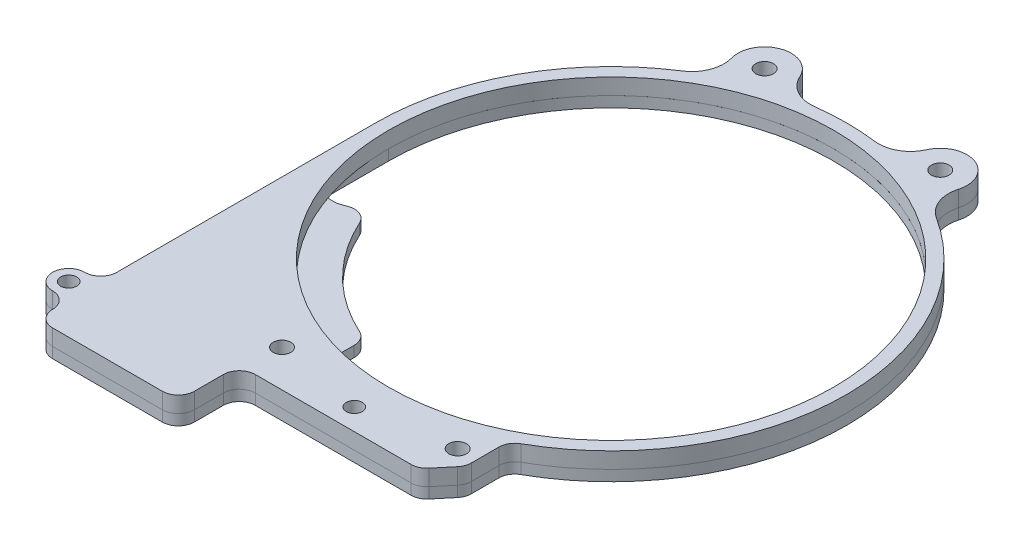
SolidWorks part; units mm, degrees
material "Thornel Mat VMA"
ref_plane "前视基准面" through (0, 0, 0) normal (0, 0, 1) x (1, 0, 0)
ref_plane "上视基准面" through (0, 0, 0) normal (0, 1, 0) x (1, 0, 0)
ref_plane "右视基准面" through (0, 0, 0) normal (1, 0, 0) x (0, 0, -1)
other "Configuration Table"
sketch "草图1" plane through (0, 0, 0) normal (0, 1, 0) x (1, 0, 0)
  line L0 (-33.3591, -12.1417) -> (-37.5877, -13.6808)
  line L1 (-13, -33.0341) -> (-13, -39.5166)
  line L2 (0, 0) -> (0, -48) construction
  line L3 (-37.5877, -13.6808) -> (-41.6, -13.6808)
  line L4 (0, 0) -> (-48, 0) construction
  line L5 (-44, 3.1363) -> (-44, -21.8637)
  line L6 (-44, -52) -> (16, -52)
  line L7 (-44, -27.8637) -> (-44, -52)
  line L8 (-44, 3.1363) -> (-44, 0)
  line L9 (0, 0) -> (16.417, 45.1052) construction
  line L10 (-44, -21.8637) -> (-44, -27.8637)
  line L11 (-41.6, 0) -> (-41.6, -13.6808)
  arc A0 (44, 0) -> (23.7553, 37.0363) centre (0, 0) ccw
  arc A1 (-13, -39.5166) -> (-41.6, 0) centre (0, 0) ccw
  arc A2 (-33.3591, -12.1417) -> (-13, -33.0341) centre (0, 0) ccw
  arc A3 (44, 0) -> (16, -52) centre (-18.2857, 0) cw
  circle A8 centre (0, -48) radius 1.5
  arc A9 (21.225, 43.7332) -> (11.8518, 47.1447) centre (16.417, 45.1052) ccw
  circle A10 centre (16.417, 45.1052) radius 1.65
  arc A11 (-21.225, 43.7332) -> (-11.8518, 47.1447) centre (-16.417, 45.1052) cw
  arc A13 (-23.7553, 37.0363) -> (-44, 0) centre (0, 0) ccw
  arc A14 (5.6088, 43.641) -> (-5.6088, 43.641) centre (0, 0) ccw
  arc A15 (23.7553, 37.0363) -> (21.225, 43.7332) centre (26.9947, 42.0867) cw
  arc A16 (5.6088, 43.641) -> (11.8518, 47.1447) centre (6.3737, 49.5921) ccw
  arc A17 (-5.6088, 43.641) -> (-11.8518, 47.1447) centre (-6.3737, 49.5921) cw
  arc A18 (-23.7553, 37.0363) -> (-21.225, 43.7332) centre (-26.9947, 42.0867) ccw
  circle A19 centre (-16.417, 45.1052) radius 1.65
  circle A20 centre (16.417, -45.1052) radius 1.65
  circle A21 centre (-16.417, -45.1052) radius 1.65
  point P6 (-13, -36.2753)
  dimension "D1" = 88
  dimension "D2" = 83.2
  dimension "D3" = 35.5
  dimension "D9" = 10
  dimension "D10" = 3.3
  dimension "D13" = 3
  dimension "D16" = 6
  dimension "D4" = 13
  dimension "D5" = 20
  dimension "D6" = 40
  dimension "D7" = 52
  dimension "D8" = 60
  dimension "D11" = 48
  dimension "D12" = 48
  dimension "D14" = 48
  dimension "D15" = 20
extrude "凸台-拉伸1" add sketch "草图1" along normal blind 2 contours A18 A13 L5 L10 L7 L6 A3 A0 A15 A9 A16 A14 A17 A11 A2 L0 L3 A1 L1 A8 A10 A19 region at (-37.4257, 0, -20.4576)
fillet "圆角1" radius 3 5 edges at (-13, 1, 39.5166) (-37.5877, 1, 13.6808) (-33.3591, 1, 12.1417) (-13, 1, 33.0341) (-41.6, 1, 13.6808)
sketch "草图3" plane through (0, 2, 0) normal (0, 1, 0) x (1, 0, 0)
  line L0 (16, -52) -> (20, -47.1918)
  line L1 (20, -47.1918) -> (20, -39.1918)
  line L2 (-44, 0) -> (-44, -52) construction
  circle A0 centre (0, 0) radius 44
  arc M7 (16, -52) -> (44, 0) centre (-18.2857, 0) ccw
  dimension "D1" = 88
  dimension "D2" = 64
  dimension "D3" = 8
extrude "切除-拉伸1" cut sketch "草图3" against normal blind 10 contours A0 L1 L0 M7 region at (29.1032, 2, 35.3583)
sketch "草图5" plane through (0, 2, 0) normal (0, 1, 0) x (1, 0, 0)
  line L0 (-44, 0) -> (-44, -52) construction
  line L1 (-17.5, -52) -> (-44, -52)
  line L2 (-17.5, -52) -> (-17.5, -63.4)
  line L3 (-17.5, -63.4) -> (-44, -63.4)
  line L4 (-44, -52) -> (-44, -63.4)
  line L5 (-44, -52) -> (16, -52) construction
  dimension "D1" = 11.4
  dimension "D2" = 26.5
extrude "凸台-拉伸2" add sketch "草图5" against normal blind 2
sketch "草图6" plane through (0, 2, 0) normal (0, 1, 0) x (1, 0, 0)
  line L1 (-44, -63.4) -> (-17.5, -63.4) construction
  line L2 (-44, 0) -> (-44, -63.4) construction
  line L4 (-50, -57.4) -> (-44, -57.4)
  line L5 (-50, -57.4) -> (-50, -51.4)
  line L6 (-50, -51.4) -> (-44, -51.4)
  line L7 (-44, -57.4) -> (-44, -51.4)
  line L8 (-50, -57.4) -> (-44, -51.4) construction
  line L9 (-50, -51.4) -> (-44, -57.4) construction
  circle A0 centre (-47, -54.4) radius 1.5
  dimension "D1" = 9
  dimension "D2" = 3
  dimension "D3" = 3
extrude "凸台-拉伸3" add sketch "草图6" against normal blind 2
fillet "圆角2" radius 3 10 edges at (-44, 1, 51.4) (-50, 1, 57.4) (-44, 1, 57.4) (-44, 1, 63.4) (-17.5, 1, 63.4) (-17.5, 1, 52) (16, 1, 52) (20, 1, 47.1918) (20, 1, 39.1918) (-50, 1, 51.4)
sketch "草图7" plane through (0, 2, 0) normal (0, 1, 0) x (1, 0, 0)
  line L6 (-41, -63.4) -> (-20.5, -63.4)
  line L7 (-17.5, -60.4) -> (-17.5, -55)
  line L8 (-14.5, -52) -> (14.5933, -52)
  line L9 (16.8996, -50.9186) -> (19.3063, -48.0257)
  line L10 (20, -46.1071) -> (20, -40.9878)
  line L11 (-44, 0) -> (-44, -48.4)
  line L12 (-41, -63.4) -> (-20.5, -63.4)
  line L13 (-17.5, -60.4) -> (-17.5, -55)
  line L14 (-14.5, -52) -> (14.5933, -52)
  line L15 (16.8996, -50.9186) -> (19.3063, -48.0257)
  line L16 (20, -46.1071) -> (20, -40.9878)
  line L17 (-44, 0) -> (-44, -48.4)
  circle A0 centre (0, 0) radius 41.6
  circle A1 centre (16.417, -45.1052) radius 1.65 construction
  circle A2 centre (0, -48) radius 1.5 construction
  circle A3 centre (-16.417, -45.1052) radius 1.65 construction
  circle A4 centre (16.417, 45.1052) radius 1.65 construction
  circle A5 centre (-16.417, 45.1052) radius 1.65 construction
  circle A6 centre (16.417, -45.1052) radius 1.65
  circle A7 centre (0, -48) radius 1.5
  circle A8 centre (-16.417, -45.1052) radius 1.65
  circle A9 centre (16.417, 45.1052) radius 1.65
  circle A10 centre (-16.417, 45.1052) radius 1.65
  circle A11 centre (-47, -54.4) radius 1.5 construction
  circle A12 centre (-47, -54.4) radius 1.5
  arc A19 (-50, -54.4) -> (-47, -57.4) centre (-47, -54.4) ccw
  arc A20 (-44, -60.4) -> (-47, -57.4) centre (-47, -60.4) ccw
  arc A21 (-44, -60.4) -> (-41, -63.4) centre (-41, -60.4) ccw
  arc A22 (-20.5, -63.4) -> (-17.5, -60.4) centre (-20.5, -60.4) ccw
  arc A23 (-14.5, -52) -> (-17.5, -55) centre (-14.5, -55) ccw
  arc A24 (14.5933, -52) -> (16.8996, -50.9186) centre (14.5933, -49) ccw
  arc A25 (19.3063, -48.0257) -> (20, -46.1071) centre (17, -46.1071) ccw
  arc A26 (21.5319, -38.3716) -> (20, -40.9878) centre (23, -40.9878) ccw
  arc A27 (21.5319, -38.3716) -> (23.7553, 37.0363) centre (0, 0) ccw
  arc A28 (21.225, 43.7332) -> (23.7553, 37.0363) centre (26.9947, 42.0867) ccw
  arc A29 (21.225, 43.7332) -> (11.8518, 47.1447) centre (16.417, 45.1052) ccw
  arc A30 (5.6088, 43.641) -> (11.8518, 47.1447) centre (6.3737, 49.5921) ccw
  arc A31 (5.6088, 43.641) -> (-5.6088, 43.641) centre (0, 0) ccw
  arc A32 (-11.8518, 47.1447) -> (-5.6088, 43.641) centre (-6.3737, 49.5921) ccw
  arc A33 (-11.8518, 47.1447) -> (-21.225, 43.7332) centre (-16.417, 45.1052) ccw
  arc A34 (-23.7553, 37.0363) -> (-21.225, 43.7332) centre (-26.9947, 42.0867) ccw
  arc A35 (-23.7553, 37.0363) -> (-44, 0) centre (0, 0) ccw
  arc A36 (-47, -51.4) -> (-44, -48.4) centre (-47, -48.4) ccw
  arc A37 (-47, -51.4) -> (-50, -54.4) centre (-47, -54.4) ccw
  arc A38 (-50, -54.4) -> (-47, -57.4) centre (-47, -54.4) ccw
  arc A39 (-44, -60.4) -> (-47, -57.4) centre (-47, -60.4) ccw
  arc A40 (-44, -60.4) -> (-41, -63.4) centre (-41, -60.4) ccw
  arc A41 (-20.5, -63.4) -> (-17.5, -60.4) centre (-20.5, -60.4) ccw
  arc A42 (-14.5, -52) -> (-17.5, -55) centre (-14.5, -55) ccw
  arc A43 (14.5933, -52) -> (16.8996, -50.9186) centre (14.5933, -49) ccw
  arc A44 (19.3063, -48.0257) -> (20, -46.1071) centre (17, -46.1071) ccw
  arc A45 (21.5319, -38.3716) -> (20, -40.9878) centre (23, -40.9878) ccw
  arc A46 (21.5319, -38.3716) -> (23.7553, 37.0363) centre (0, 0) ccw
  arc A47 (21.225, 43.7332) -> (23.7553, 37.0363) centre (26.9947, 42.0867) ccw
  arc A48 (21.225, 43.7332) -> (11.8518, 47.1447) centre (16.417, 45.1052) ccw
  arc A49 (5.6088, 43.641) -> (11.8518, 47.1447) centre (6.3737, 49.5921) ccw
  arc A50 (5.6088, 43.641) -> (-5.6088, 43.641) centre (0, 0) ccw
  arc A51 (-11.8518, 47.1447) -> (-5.6088, 43.641) centre (-6.3737, 49.5921) ccw
  arc A52 (-11.8518, 47.1447) -> (-21.225, 43.7332) centre (-16.417, 45.1052) ccw
  arc A53 (-23.7553, 37.0363) -> (-21.225, 43.7332) centre (-26.9947, 42.0867) ccw
  arc A54 (-23.7553, 37.0363) -> (-44, 0) centre (0, 0) ccw
  arc A55 (-47, -51.4) -> (-44, -48.4) centre (-47, -48.4) ccw
  arc A56 (-47, -51.4) -> (-50, -54.4) centre (-47, -54.4) ccw
  dimension "D2" = 83.2
  dimension "D1" = 0
extrude "凸台-拉伸4" add sketch "草图7" along normal blind 3 separate body
